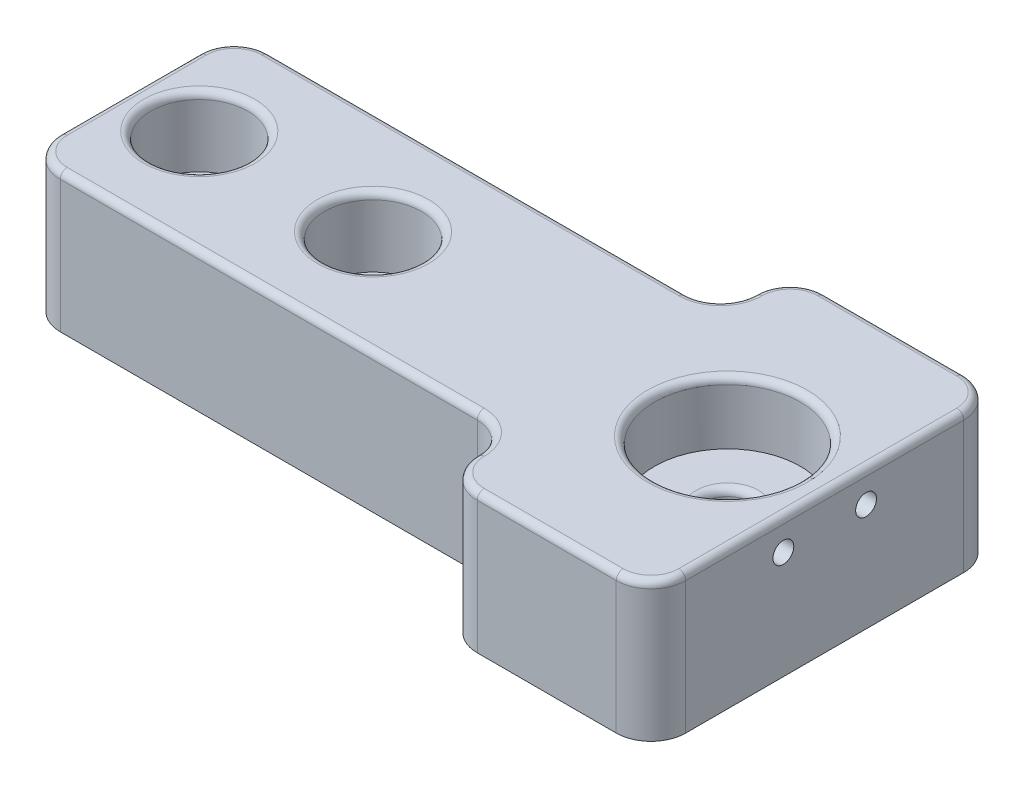
SolidWorks part; units mm, degrees
ref_plane "Front Plane" through (0, 0, 0) normal (0, 0, 1) x (1, 0, 0)
ref_plane "Top Plane" through (0, 0, 0) normal (0, 1, 0) x (1, 0, 0)
ref_plane "Right Plane" through (0, 0, 0) normal (1, 0, 0) x (0, 0, -1)
sketch "Sketch1" plane through (0, 0, 0) normal (0, 1, 0) x (1, 0, 0)
  line L1 (-50, -15) -> (50, -15)
  line L2 (-50, -15) -> (-50, 15)
  line L3 (-50, 15) -> (50, 15)
  line L4 (50, -15) -> (50, 15)
  line L5 (-50, -15) -> (50, 15) construction
  line L6 (-50, 15) -> (50, -15) construction
  circle A0 centre (36, 0) radius 3.5
  circle A1 centre (-40, 0) radius 3.5
  circle A2 centre (-15, 0) radius 3.5
  point P0 (0, 0)
  point P8 (50, 0)
  point P13 (-50, 0)
  dimension "D4" = 7
  dimension "D5" = 7
  dimension "D1" = 30
  dimension "D2" = 100
  dimension "D3" = 14
  dimension "D6" = 10
  dimension "D7" = 25
extrude "Boss-Extrude1" add sketch "Sketch1" along normal blind 20
sketch "Sketch2" plane through (0, 20, 0) normal (0, 1, 0) x (1, 0, 0)
  circle A0 centre (36, 0) radius 10.5
  dimension "D1" = 21
extrude "Cut-Extrude1" cut sketch "Sketch2" against normal blind 9
sketch "Sketch3" plane through (50, 0, 0) normal (1, 0, 0) x (0, 0, -1)
  line L0 (10.5, 11) -> (-10.5, 11) construction
  line L1 (10.5, 20) -> (-10.5, 20) construction
  line L2 (10.5, 11) -> (-10.5, 11) construction
  line L3 (10.5, 20) -> (-10.5, 20) construction
  line L4 (-10.5, 20) -> (-10.5, 11) construction
  line L5 (10.5, 20) -> (10.5, 11) construction
  line L6 (10.5, 15.5) -> (5.95, 15.5) construction
  line L7 (-5.95, 15.5) -> (-10.5, 15.5) construction
  circle A0 centre (-5.95, 15.5) radius 1.5
  circle A1 centre (5.95, 15.5) radius 1.5
  point P8 (10.5, 15.5)
  dimension "D2" = 3
  dimension "D1" = 11.9
extrude "Cut-Extrude2" cut sketch "Sketch3" against normal up to next
sketch "Sketch4" plane through (0, 20, 0) normal (0, 1, 0) x (1, 0, 0)
  line L0 (20, 15) -> (20, 25)
  line L1 (50, 15) -> (-50, 15) construction
  line L2 (20, 25) -> (50, 25)
  line L4 (50, -25) -> (20, -25)
  line L5 (20, -25) -> (20, -15)
  line L6 (-50, -15) -> (50, -15) construction
  line L7 (20, -15) -> (50, -15)
  line L9 (50, 15) -> (20, 15)
  line L10 (50, 25) -> (50, 15)
  line L11 (50, -25) -> (50, -15)
  dimension "D1" = 50
  dimension "D3" = 30
extrude "Boss-Extrude2" add sketch "Sketch4" against normal up to surface (20 mm away) up to face at (-40, 0, 3.5)
sketch "Sketch5" plane through (0, 20, 0) normal (0, 1, 0) x (1, 0, 0)
  circle A0 centre (-40, 0) radius 7
  circle A1 centre (-15, 0) radius 7
  dimension "D1" = 14
extrude "Cut-Extrude3" cut sketch "Sketch5" against normal offset from surface (10 mm away) 10 up to face at (-40, 0, 3.5)
fillet "Fillet1" radius 5 8 edges at (-50, 10, -15) (-50, 10, 15) (50, 10, 25) (20, 10, -15) (20, 10, 15) (20, 10, 25) (50, 10, -25) (20, 10, -25)
fillet "Fillet2" radius 1 20 edges at (-48.5355, 20, 13.5355) (-50, 20, 0) (-48.5355, 20, -13.5355) (-15, 20, -15) (50, 20, 0) (-15, 20, 15) (36, 11, 3.5) (36, 20, 10.5) (18.5355, 20, -16.4645) (21.4645, 20, -23.5355) (35, 20, -25) (48.5355, 20, -23.5355) (48.5355, 20, 23.5355) (35, 20, 25) (21.4645, 20, 23.5355) (18.5355, 20, 16.4645) (-40, 20, 7) (-15, 20, 7) (-15, 10, -3.5) (-40, 10, -3.5)
